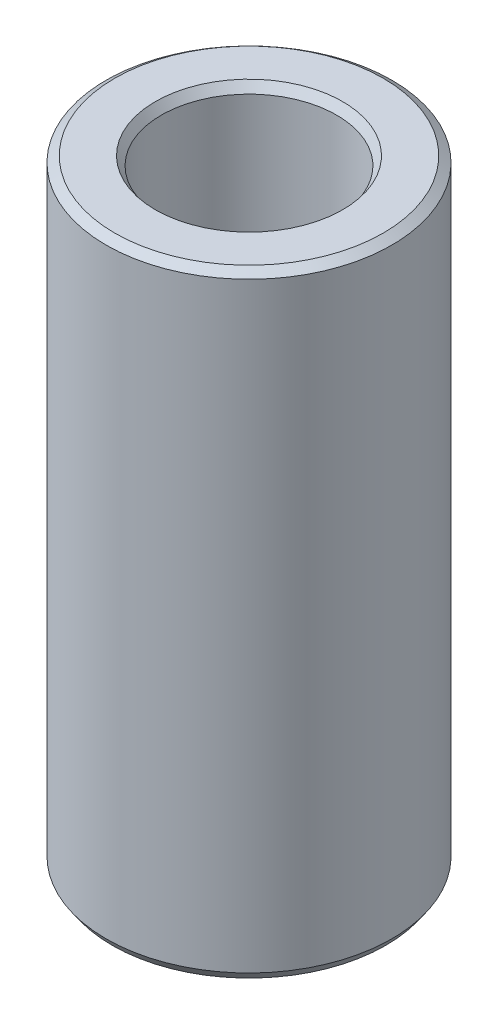
SolidWorks part; units mm, degrees
ref_plane "Front Plane" through (0, 0, 0) normal (0, 0, 1) x (1, 0, 0)
ref_plane "Top Plane" through (0, 0, 0) normal (0, 1, 0) x (1, 0, 0)
ref_plane "Right Plane" through (0, 0, 0) normal (1, 0, 0) x (0, 0, -1)
sketch "Sketch1" plane through (0, 0, 0) normal (0, 1, 0) x (1, 0, 0)
  circle A0 centre (0, 0) radius 12.5
  dimension "SLEEVE_OD" = 25
extrude "Boss-Extrude1" add sketch "Sketch1" along normal blind 53.8508
sketch "Sketch2" plane through (0, 0, 0) normal (0, 1, 0) x (1, 0, 0)
  circle A0 centre (0, 0) radius 7.6709
  dimension "BORE_D" = 15.3419
extrude "Cut-Extrude1" cut sketch "Sketch2" along normal through all
chamfer "Chamfer1" distance 0.5273 angle 55.208 4 edges at (0, 53.8508, 7.6709) (0, 0, 7.6709) (0, 0, 12.5) (0, 53.8508, 12.5) first distance on face at (0, 53.8508, 7.6709) first distance on face at (0, 0, 7.6709) first distance on face at (0, 53.8508, 12.5)
